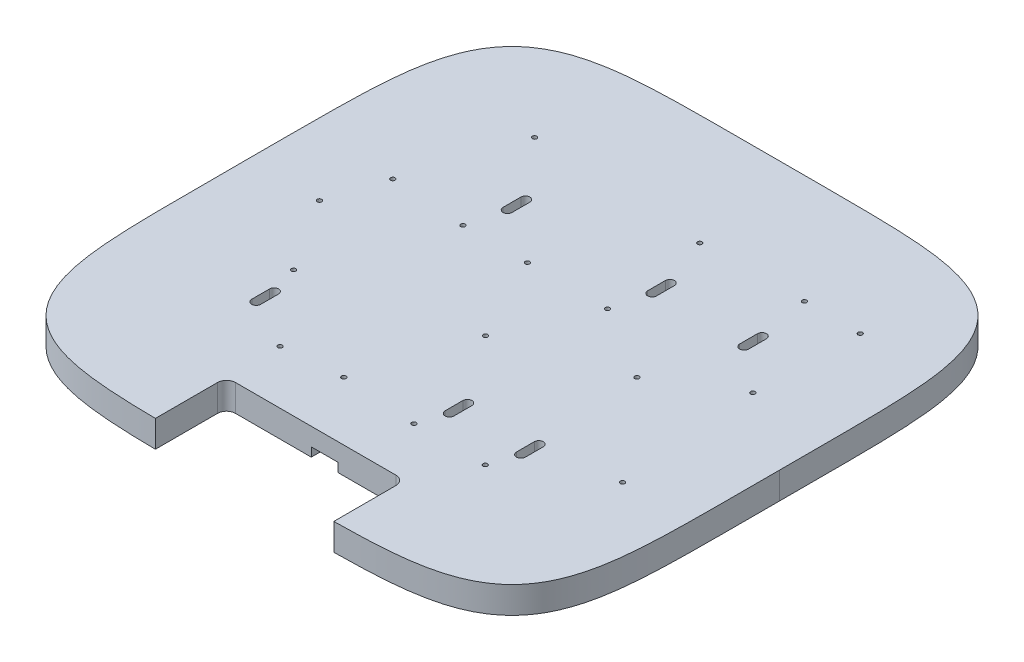
SolidWorks part; units mm, degrees
material "Сосна"
ref_plane "Спереди" through (0, 0, 0) normal (0, 0, 1) x (1, 0, 0)
ref_plane "Сверху" through (0, 0, 0) normal (0, 1, 0) x (1, 0, 0)
ref_plane "Справа" through (0, 0, 0) normal (1, 0, 0) x (0, 0, -1)
sketch "Эскиз основания" plane through (0, 0, 0) normal (0, 1, 0) x (1, 0, 0)
  line L0 (-90, -220) -> (90, -220)
  line L5 (-100, -230) -> (-100, -299.7527)
  line L7 (100, -230) -> (100, -299.7527)
  arc A6 (90, -220) -> (100, -230) centre (90, -230) cw
  arc A7 (-90, -220) -> (-100, -230) centre (-90, -230) ccw
  spline S0 degree 4 poles (300, 0) (299.9998, 8.6944) (299.9997, 21.736) (300.0012, 36.9513) (299.9906, 54.3402) (299.9623, 71.729) (299.8757, 93.4652) (299.6029, 117.242) (298.6794, 143.0506) (297.1967, 163.2872) (295.5862, 177.9573) (293.4888, 191.5009) (291.1341, 202.8581) (288.4089, 213.0451) (285.4103, 222.0487) (282.2757, 229.8814) (278.6208, 237.487) (274.4032, 244.7975) (269.5959, 251.7363) (264.1954, 258.2254) (258.2254, 264.1954) (251.7362, 269.596) (244.7974, 274.4032) (237.487, 278.6209) (229.8814, 282.2757) (222.0487, 285.4104) (213.0451, 288.4089) (202.8581, 291.1341) (191.5009, 293.4888) (177.9573, 295.5862) (163.2872, 297.1967) (143.0506, 298.6794) (117.242, 299.6029) (93.4652, 299.8758) (71.729, 299.9623) (54.3402, 299.9907) (36.9513, 300.0012) (21.736, 299.9997) (8.6944, 299.9998) (0, 300) knots 0 0 0 0 0 0.064453 0.09668 0.112793 0.128906 0.193359 0.257812 0.289062 0.320312 0.34375 0.367188 0.390625 0.40625 0.421875 0.4375 0.453125 0.46875 0.484375 0.5 0.515625 0.53125 0.546875 0.5625 0.578125 0.59375 0.609375 0.632812 0.65625 0.679688 0.710938 0.742188 0.806641 0.871094 0.887207 0.90332 0.935547 1 1 1 1 1 construction
  spline S1 degree 4 poles (300, 0) (299.9998, 8.6944) (299.9997, 21.736) (300.0012, 36.9513) (299.9906, 54.3402) (299.9623, 71.729) (299.8757, 93.4652) (299.6029, 117.242) (298.6794, 143.0506) (297.1967, 163.2872) (295.5862, 177.9573) (293.4888, 191.5009) (291.1341, 202.8581) (288.4089, 213.0451) (285.4103, 222.0487) (282.2757, 229.8814) (278.6208, 237.487) (274.4032, 244.7975) (269.5959, 251.7363) (264.1954, 258.2254) (258.2254, 264.1954) (251.7362, 269.596) (244.7974, 274.4032) (237.487, 278.6209) (229.8814, 282.2757) (222.0487, 285.4104) (213.0451, 288.4089) (202.8581, 291.1341) (191.5009, 293.4888) (177.9573, 295.5862) (163.2872, 297.1967) (143.0506, 298.6794) (117.242, 299.6029) (93.4652, 299.8758) (71.729, 299.9623) (54.3402, 299.9907) (36.9513, 300.0012) (21.736, 299.9997) (8.6944, 299.9998) (0, 300) knots 0 0 0 0 0 0.064453 0.09668 0.112793 0.128906 0.193359 0.257812 0.289062 0.320312 0.34375 0.367188 0.390625 0.40625 0.421875 0.4375 0.453125 0.46875 0.484375 0.5 0.515625 0.53125 0.546875 0.5625 0.578125 0.59375 0.609375 0.632812 0.65625 0.679688 0.710938 0.742188 0.806641 0.871094 0.887207 0.90332 0.935547 1 1 1 1 1
  spline S2 degree 4 poles (300, 0) (299.9998, -8.6944) (299.9997, -21.736) (300.0012, -36.9513) (299.9907, -54.3402) (299.9623, -71.729) (299.8758, -93.4652) (299.6029, -117.242) (298.6794, -143.0506) (297.1967, -163.2872) (295.5862, -177.9573) (293.4888, -191.5009) (291.1341, -202.8581) (288.4089, -213.0451) (285.4104, -222.0487) (282.2757, -229.8814) (278.6209, -237.487) (274.4032, -244.7975) (269.596, -251.7363) (264.1954, -258.2254) (258.2254, -264.1954) (251.7363, -269.596) (244.7975, -274.4032) (237.487, -278.6209) (229.8814, -282.2757) (222.0487, -285.4104) (213.0452, -288.4089) (202.8582, -291.1341) (191.5009, -293.4889) (177.9574, -295.5863) (163.2872, -297.1967) (143.0506, -298.6794) (117.242, -299.6029) (93.4652, -299.8758) (71.729, -299.9624) (54.3403, -299.9907) (36.9514, -300.0013) (21.7361, -299.9997) (8.6945, -299.9999) (0, -300) knots 0 0 0 0 0 0.064453 0.09668 0.112793 0.128906 0.193359 0.257812 0.289062 0.320312 0.34375 0.367188 0.390625 0.40625 0.421875 0.4375 0.453125 0.46875 0.484375 0.5 0.515625 0.53125 0.546875 0.5625 0.578125 0.59375 0.609375 0.632812 0.65625 0.679688 0.710938 0.742188 0.806641 0.871094 0.887207 0.90332 0.935547 1 1 1 1 1 construction
  spline S3 degree 4 poles (300, 0) (299.9998, -8.6944) (299.9997, -21.736) (300.0012, -36.9513) (299.9907, -54.3402) (299.9623, -71.729) (299.8758, -93.4652) (299.6029, -117.242) (298.6794, -143.0506) (297.1967, -163.2872) (295.5862, -177.9573) (293.4888, -191.5009) (291.1341, -202.8581) (288.4089, -213.0451) (285.4104, -222.0487) (282.2757, -229.8814) (278.6209, -237.487) (274.4032, -244.7975) (269.596, -251.7363) (264.1954, -258.2254) (258.2254, -264.1954) (251.7363, -269.596) (244.7975, -274.4032) (237.487, -278.6209) (229.8814, -282.2757) (222.0487, -285.4104) (213.0452, -288.4089) (202.8582, -291.1341) (191.5009, -293.4889) (177.9574, -295.5863) (163.2872, -297.1967) (143.0506, -298.6794) (124.8501, -299.3307) (110.8596, -299.611) (101.083, -299.7393) (100, -299.7527) knots 0 0 0 0 0 0.064453 0.09668 0.112793 0.128906 0.193359 0.257812 0.289062 0.320312 0.34375 0.367188 0.390625 0.40625 0.421875 0.4375 0.453125 0.46875 0.484375 0.5 0.515625 0.53125 0.546875 0.5625 0.578125 0.59375 0.609375 0.632812 0.65625 0.679688 0.710938 0.742188 0.806641 0.81467 0.81467 0.81467 0.81467 0.81467
  spline S4 degree 4 poles (-300, 0) (-299.9998, 8.6944) (-299.9997, 21.736) (-300.0012, 36.9513) (-299.9906, 54.3402) (-299.9623, 71.729) (-299.8757, 93.4652) (-299.6029, 117.242) (-298.6794, 143.0506) (-297.1967, 163.2872) (-295.5862, 177.9573) (-293.4888, 191.5009) (-291.1341, 202.8581) (-288.4089, 213.0451) (-285.4103, 222.0487) (-282.2757, 229.8814) (-278.6208, 237.487) (-274.4032, 244.7975) (-269.5959, 251.7363) (-264.1954, 258.2254) (-258.2254, 264.1954) (-251.7362, 269.596) (-244.7974, 274.4032) (-237.487, 278.6209) (-229.8814, 282.2757) (-222.0487, 285.4104) (-213.0451, 288.4089) (-202.8581, 291.1341) (-191.5009, 293.4888) (-177.9573, 295.5862) (-163.2872, 297.1967) (-143.0506, 298.6794) (-117.242, 299.6029) (-93.4652, 299.8758) (-71.729, 299.9623) (-54.3402, 299.9907) (-36.9513, 300.0012) (-21.736, 299.9997) (-8.6944, 299.9998) (0, 300) knots 0 0 0 0 0 0.064453 0.09668 0.112793 0.128906 0.193359 0.257812 0.289062 0.320312 0.34375 0.367188 0.390625 0.40625 0.421875 0.4375 0.453125 0.46875 0.484375 0.5 0.515625 0.53125 0.546875 0.5625 0.578125 0.59375 0.609375 0.632812 0.65625 0.679688 0.710938 0.742188 0.806641 0.871094 0.887207 0.90332 0.935547 1 1 1 1 1 construction
  spline S5 degree 4 poles (-300, 0) (-299.9998, 8.6944) (-299.9997, 21.736) (-300.0012, 36.9513) (-299.9906, 54.3402) (-299.9623, 71.729) (-299.8757, 93.4652) (-299.6029, 117.242) (-298.6794, 143.0506) (-297.1967, 163.2872) (-295.5862, 177.9573) (-293.4888, 191.5009) (-291.1341, 202.8581) (-288.4089, 213.0451) (-285.4103, 222.0487) (-282.2757, 229.8814) (-278.6208, 237.487) (-274.4032, 244.7975) (-269.5959, 251.7363) (-264.1954, 258.2254) (-258.2254, 264.1954) (-251.7362, 269.596) (-244.7974, 274.4032) (-237.487, 278.6209) (-229.8814, 282.2757) (-222.0487, 285.4104) (-213.0451, 288.4089) (-202.8581, 291.1341) (-191.5009, 293.4888) (-177.9573, 295.5862) (-163.2872, 297.1967) (-143.0506, 298.6794) (-117.242, 299.6029) (-93.4652, 299.8758) (-71.729, 299.9623) (-54.3402, 299.9907) (-36.9513, 300.0012) (-21.736, 299.9997) (-8.6944, 299.9998) (0, 300) knots 0 0 0 0 0 0.064453 0.09668 0.112793 0.128906 0.193359 0.257812 0.289062 0.320312 0.34375 0.367188 0.390625 0.40625 0.421875 0.4375 0.453125 0.46875 0.484375 0.5 0.515625 0.53125 0.546875 0.5625 0.578125 0.59375 0.609375 0.632812 0.65625 0.679688 0.710938 0.742188 0.806641 0.871094 0.887207 0.90332 0.935547 1 1 1 1 1
  spline S6 degree 4 poles (-300, 0) (-299.9998, -8.6944) (-299.9997, -21.736) (-300.0012, -36.9513) (-299.9907, -54.3402) (-299.9623, -71.729) (-299.8758, -93.4652) (-299.6029, -117.242) (-298.6794, -143.0506) (-297.1967, -163.2872) (-295.5862, -177.9573) (-293.4888, -191.5009) (-291.1341, -202.8581) (-288.4089, -213.0451) (-285.4104, -222.0487) (-282.2757, -229.8814) (-278.6209, -237.487) (-274.4032, -244.7975) (-269.596, -251.7363) (-264.1954, -258.2254) (-258.2254, -264.1954) (-251.7363, -269.596) (-244.7975, -274.4032) (-237.487, -278.6209) (-229.8814, -282.2757) (-222.0487, -285.4104) (-213.0452, -288.4089) (-202.8582, -291.1341) (-191.5009, -293.4889) (-177.9574, -295.5863) (-163.2872, -297.1967) (-143.0506, -298.6794) (-117.242, -299.6029) (-93.4652, -299.8758) (-71.729, -299.9624) (-54.3403, -299.9907) (-36.9514, -300.0013) (-21.7361, -299.9997) (-8.6945, -299.9999) (0, -300) knots 0 0 0 0 0 0.064453 0.09668 0.112793 0.128906 0.193359 0.257812 0.289062 0.320312 0.34375 0.367188 0.390625 0.40625 0.421875 0.4375 0.453125 0.46875 0.484375 0.5 0.515625 0.53125 0.546875 0.5625 0.578125 0.59375 0.609375 0.632812 0.65625 0.679688 0.710938 0.742188 0.806641 0.871094 0.887207 0.90332 0.935547 1 1 1 1 1 construction
  spline S7 degree 4 poles (-300, 0) (-299.9998, -8.6944) (-299.9997, -21.736) (-300.0012, -36.9513) (-299.9907, -54.3402) (-299.9623, -71.729) (-299.8758, -93.4652) (-299.6029, -117.242) (-298.6794, -143.0506) (-297.1967, -163.2872) (-295.5862, -177.9573) (-293.4888, -191.5009) (-291.1341, -202.8581) (-288.4089, -213.0451) (-285.4104, -222.0487) (-282.2757, -229.8814) (-278.6209, -237.487) (-274.4032, -244.7975) (-269.596, -251.7363) (-264.1954, -258.2254) (-258.2254, -264.1954) (-251.7363, -269.596) (-244.7975, -274.4032) (-237.487, -278.6209) (-229.8814, -282.2757) (-222.0487, -285.4104) (-213.0452, -288.4089) (-202.8582, -291.1341) (-191.5009, -293.4889) (-177.9574, -295.5863) (-163.2872, -297.1967) (-143.0506, -298.6794) (-124.8501, -299.3307) (-110.8596, -299.611) (-101.083, -299.7393) (-100, -299.7527) knots 0 0 0 0 0 0.064453 0.09668 0.112793 0.128906 0.193359 0.257812 0.289062 0.320312 0.34375 0.367188 0.390625 0.40625 0.421875 0.4375 0.453125 0.46875 0.484375 0.5 0.515625 0.53125 0.546875 0.5625 0.578125 0.59375 0.609375 0.632812 0.65625 0.679688 0.710938 0.742188 0.806641 0.81467 0.81467 0.81467 0.81467 0.81467
  point P2 (0, 0)
  point P3 (0, 0)
  point P4 (0, 0)
  point P6 (0, 0)
  point P7 (0, 0)
  point P8 (7.0585, 300)
  point P9 (0, 0)
  point P10 (0, 0)
  point P15 (0, 0)
  point P17 (-1101.0099, 325.3296)
  point P18 (-34.3061, 430.4716)
  point P21 (-820.0172, 325.7581)
  point P29 (0, 0)
  point P32 (-887.2092, 339.7177)
  point P36 (-876.459, 565.4724)
  dimension "D10" = 10
  dimension "D6" = 200
  dimension "D8" = 100
  dimension "D2" = 220
  dimension "D3" = 599.9999
extrude "Основание" add sketch "Эскиз основания" against normal blind 30
sketch "Эскиз разметки под крепёж" plane through (0, 0, 0) normal (0, 1, 0) x (1, 0, 0)
  line L0 (-372.0217, 60) -> (388.5777, 60) construction
  line L1 (-372.0217, -160) -> (374.4585, -160) construction
  line L2 (0, -364.7935) -> (0, 383.2318) construction
  circle A0 centre (-115, 60) radius 2.5
  circle A1 centre (47, 60) radius 2.5
  circle A2 centre (210, 60) radius 2.5
  circle A3 centre (-100, -160) radius 2.5
  circle A4 centre (50, -160) radius 2.5
  circle A5 centre (130, -160) radius 2.5
  circle A6 centre (-42.72, 60) radius 2.5
  circle A7 centre (-199.29, 65.75) radius 2.5
  circle A8 centre (-160.19, 185.5) radius 2.5
  circle A9 centre (34.8068, 175.55) radius 2.5
  circle A10 centre (150.2162, 177.55) radius 2.5
  circle A11 centre (212.76, 177.55) radius 2.5
  circle A12 centre (-166.6668, -78.149) radius 2.5
  circle A13 centre (-219.52, 3.7) radius 2.5
  circle A14 centre (-34.29, -154.25) radius 2.5
  circle A15 centre (4.81, -34.5) radius 2.5
  circle A16 centre (223.895, -100) radius 2.5
  circle A17 centre (130, 10) radius 2.5
  dimension "D2" = 5
  dimension "D3" = 5
  dimension "D4" = 5
  dimension "D9" = 5
  dimension "D10" = 5
  dimension "D11" = 5
  dimension "D7" = 5
  dimension "D18" = 5
  dimension "D19" = 5
  dimension "D20" = 5
  dimension "D21" = 5
  dimension "D22" = 5
  dimension "D23" = 5
  dimension "D24" = 5
  dimension "D25" = 5
  dimension "D26" = 5
  dimension "D27" = 5
  dimension "D28" = 5
  dimension "D5" = 60
  dimension "D6" = 220
  dimension "D8" = 130
  dimension "D12" = 50
  dimension "D13" = 100
  dimension "D14" = 210
  dimension "D15" = 47
  dimension "D16" = 115
  dimension "D17" = 89.72
  dimension "D29" = 84.29
  dimension "D30" = 5.75
  dimension "D31" = 125.5
  dimension "D32" = 45.19
  dimension "D33" = 12.1932
  dimension "D34" = 115.55
  dimension "D35" = 2.76
  dimension "D36" = 117.55
  dimension "D37" = 59.7838
  dimension "D38" = 84.29
  dimension "D39" = 5.75
  dimension "D40" = 125.5
  dimension "D41" = 45.19
  dimension "D42" = 81.851
  dimension "D43" = 66.6668
  dimension "D44" = 163.7
  dimension "D45" = 119.52
  dimension "D46" = 170
  dimension "D47" = 93.895
  dimension "D48" = 60
extrude "Разметка под крепёж" cut sketch "Эскиз разметки под крепёж" against normal through all
sketch "Эскиз проерзей для проводов" plane through (0, 0, 0) normal (0, 1, 0) x (1, 0, 0)
  line L0 (-105, 120) -> (-105, 100) construction
  line L1 (-100, 120) -> (-100, 100)
  line L2 (-110, 120) -> (-110, 100)
  line L3 (57, 120) -> (57, 100) construction
  line L4 (62, 120) -> (62, 100)
  line L5 (52, 120) -> (52, 100)
  line L6 (160.2162, 120) -> (160.2162, 100) construction
  line L7 (165.2162, 120) -> (165.2162, 100)
  line L8 (155.2162, 120) -> (155.2162, 100)
  line L9 (-156.6668, -110) -> (-156.6668, -130) construction
  line L10 (-151.6668, -110) -> (-151.6668, -130)
  line L11 (-161.6668, -110) -> (-161.6668, -130)
  line L12 (60, -110) -> (60, -130) construction
  line L13 (65, -110) -> (65, -130)
  line L14 (55, -110) -> (55, -130)
  line L15 (140, -110) -> (140, -130) construction
  line L16 (145, -110) -> (145, -130)
  line L17 (135, -110) -> (135, -130)
  arc A0 (-100, 120) -> (-110, 120) centre (-105, 120) ccw
  arc A1 (-110, 100) -> (-100, 100) centre (-105, 100) ccw
  circle A2 centre (150.2162, 177.55) radius 2.5 construction
  circle A3 centre (-115, 60) radius 2.5 construction
  arc A4 (62, 120) -> (52, 120) centre (57, 120) ccw
  arc A5 (52, 100) -> (62, 100) centre (57, 100) ccw
  circle A6 centre (47, 60) radius 2.5 construction
  arc A7 (165.2162, 120) -> (155.2162, 120) centre (160.2162, 120) ccw
  arc A8 (155.2162, 100) -> (165.2162, 100) centre (160.2162, 100) ccw
  arc A10 (-151.6668, -110) -> (-161.6668, -110) centre (-156.6668, -110) ccw
  arc A11 (-161.6668, -130) -> (-151.6668, -130) centre (-156.6668, -130) ccw
  arc A12 (65, -110) -> (55, -110) centre (60, -110) ccw
  arc A13 (55, -130) -> (65, -130) centre (60, -130) ccw
  arc A14 (145, -110) -> (135, -110) centre (140, -110) ccw
  arc A15 (135, -130) -> (145, -130) centre (140, -130) ccw
  circle A16 centre (-166.6668, -78.149) radius 2.5 construction
  circle A17 centre (50, -160) radius 2.5 construction
  circle A18 centre (130, -160) radius 2.5 construction
  point P2 (-105, 110)
  point P12 (57, 110)
  point P21 (160.2162, 110)
  point P28 (-156.6668, -120)
  point P35 (60, -120)
  point P42 (140, -120)
  dimension "D1" = 5
  dimension "D2" = 100
  dimension "D4" = 5
  dimension "D6" = 5
  dimension "D7" = 5
  dimension "D9" = 5
  dimension "D5" = 5
  dimension "D11" = 5
  dimension "D12" = 5
  dimension "D13" = 5
  dimension "D17" = 5
  dimension "D18" = 5
  dimension "D19" = 5
  dimension "D3" = 20
  dimension "D8" = 20
  dimension "D10" = 20
  dimension "D14" = 20
  dimension "D15" = 20
  dimension "D16" = 20
  dimension "D20" = 110
extrude "Прорезь для проводов" cut sketch "Эскиз проерзей для проводов" against normal through all
ref_plane "Плоскость кабель-канала" through (0, -30, 0) normal (0, 1, 0) x (1, 0, 0)
sketch "Эскиз кабель-канала" plane through (0, -30, 0) normal (0, 1, 0) x (1, 0, 0)
  line L0 (-110, 120) -> (-110, 100) construction
  line L1 (-105, 95) -> (70, 95)
  line L2 (-110, 100) -> (-110, 120)
  line L3 (-105, 125) -> (160.2162, 125)
  line L4 (165.2162, 100) -> (165.2162, 120)
  line L5 (165.2162, 100) -> (165.2162, 120) construction
  line L6 (145, -130) -> (145, -110) construction
  line L7 (-156.6668, -105) -> (70, -105)
  line L8 (-161.6668, -110) -> (-161.6668, -130)
  line L9 (-156.6668, -135) -> (-10, -135)
  line L10 (145, -110) -> (145, -130)
  line L11 (-161.6668, -110) -> (-161.6668, -130) construction
  line L12 (-90, -220) -> (90, -220) construction
  line L14 (75, 90) -> (75, -100)
  line L16 (105, 90) -> (105, -100)
  line L18 (-5, -140) -> (-5, -220)
  line L19 (-5, -220) -> (25, -220)
  line L20 (25, -140) -> (25, -220)
  line L21 (110, 95) -> (160.2162, 95)
  line L22 (110, -105) -> (140, -105)
  line L23 (30, -135) -> (140, -135)
  arc A0 (160.2162, 125) -> (165.2162, 120) centre (160.2162, 120) cw
  arc A1 (160.2162, 95) -> (165.2162, 100) centre (160.2162, 100) ccw
  arc A2 (-105, 95) -> (-110, 100) centre (-105, 100) cw
  arc A3 (-110, 120) -> (-105, 125) centre (-105, 120) cw
  arc A4 (140, -105) -> (145, -110) centre (140, -110) cw
  arc A5 (140, -135) -> (145, -130) centre (140, -130) ccw
  arc A6 (-161.6668, -130) -> (-156.6668, -135) centre (-156.6668, -130) ccw
  arc A7 (-156.6668, -105) -> (-161.6668, -110) centre (-156.6668, -110) ccw
  arc A8 (-10, -135) -> (-5, -140) centre (-10, -140) cw
  arc A9 (30, -135) -> (25, -140) centre (30, -140) ccw
  arc A10 (75, -100) -> (70, -105) centre (70, -100) cw
  arc A11 (110, -105) -> (105, -100) centre (110, -100) cw
  arc A12 (110, 95) -> (105, 90) centre (110, 90) ccw
  arc A13 (70, 95) -> (75, 90) centre (70, 90) cw
  point P15 (-110, 95)
  point P18 (-110, 125)
  point P29 (145, -105)
  point P32 (145, -135)
  point P57 (105, -105)
  dimension "D3" = 5
  dimension "D6" = 5
  dimension "D11" = 5
  dimension "D1" = 30
  dimension "D2" = 95
  dimension "D4" = 30
  dimension "D5" = 105
  dimension "D7" = 30
  dimension "D8" = 30
  dimension "D9" = 5
  dimension "D10" = 75
extrude "Каебель-канал" cut sketch "Эскиз кабель-канала" along normal blind 10
equation "\"box_width\"= 200мм"
equation "\"box_height\"= 80мм"
equation "\"D6@Эскиз основания\"=\"box_width\""
equation "\"drill\"= 5мм"
equation "\"D2@Эскиз разметки под крепёж\" = \"drill\""
equation "\"D3@Эскиз разметки под крепёж\" = \"drill\""
equation "\"D4@Эскиз разметки под крепёж\" = \"drill\""
equation "\"D9@Эскиз разметки под крепёж\" = \"drill\""
equation "\"D10@Эскиз разметки под крепёж\" = \"drill\""
equation "\"D11@Эскиз разметки под крепёж\" = \"drill\""
equation "\"D7@Эскиз разметки под крепёж\"=\"drill\""
equation "\"D18@Эскиз разметки под крепёж\"=\"drill\""
equation "\"D19@Эскиз разметки под крепёж\"=\"drill\""
equation "\"D20@Эскиз разметки под крепёж\"=\"drill\""
equation "\"D21@Эскиз разметки под крепёж\"=\"drill\""
equation "\"D22@Эскиз разметки под крепёж\"=\"drill\""
equation "\"D23@Эскиз разметки под крепёж\"=\"drill\""
equation "\"D24@Эскиз разметки под крепёж\"=\"drill\""
equation "\"D25@Эскиз разметки под крепёж\"=\"drill\""
equation "\"D26@Эскиз разметки под крепёж\"=\"drill\""
equation "\"D27@Эскиз разметки под крепёж\"=\"drill\""
equation "\"D28@Эскиз разметки под крепёж\"=\"drill\""
equation "\"D1@Основание\"=\"width\""
